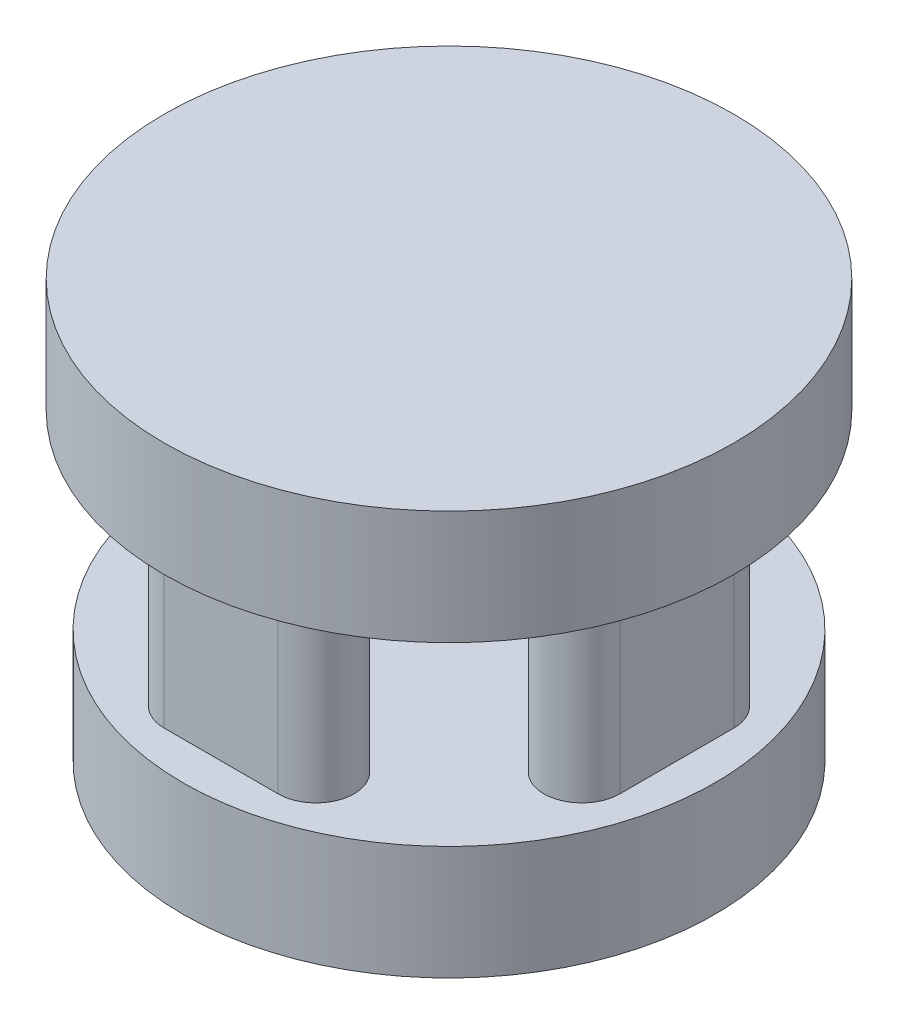
SolidWorks part; units mm, degrees
ref_plane "Front Plane" through (0, 0, 0) normal (0, 0, 1) x (1, 0, 0)
ref_plane "Top Plane" through (0, 0, 0) normal (0, 1, 0) x (1, 0, 0)
ref_plane "Right Plane" through (0, 0, 0) normal (1, 0, 0) x (0, 0, -1)
sketch "Sketch1" plane through (0, 0, 0) normal (0, 1, 0) x (1, 0, 0)
  circle A0 centre (0, 0) radius 9.525
  dimension "D1" = 19.05
extrude "button top" add sketch "Sketch1" along normal blind 3.81
sketch "Sketch2" plane through (0, 0, 0) normal (0, -1, 0) x (1, 0, 0)
  line L9 (-1.905, 6.35) -> (1.905, 6.35) construction
  line L10 (-1.905, 7.62) -> (1.905, 7.62)
  line L11 (-1.905, 5.08) -> (1.905, 5.08)
  arc A6 (-1.905, 7.62) -> (-1.905, 5.08) centre (-1.905, 6.35) ccw
  arc A7 (1.905, 5.08) -> (1.905, 7.62) centre (1.905, 6.35) ccw
  point P22 (0, 6.35)
  dimension "D2" = 1.27
  dimension "D1" = 6.35
  dimension "D8" = 3.81
extrude "connecting leg" add sketch "Sketch2" along normal blind 6.35
ref_axis "central axis" through (0, 3.81, 0) along (0, -1, 0)
pattern_circular "moar legs" count 4 over 360 about axis through (0, 3.81, 0) along (0, -1, 0) of "connecting leg"
ref_plane "base plane" through (0, -6.35, 0) normal (0, -1, 0) x (-1, 0, 0)
sketch "Sketch3" plane through (0, -6.35, 0) normal (0, -1, 0) x (-1, 0, 0)
  circle A0 centre (0, 0) radius 8.89
extrude "base" add sketch "Sketch3" along normal blind 3.81 separate body
